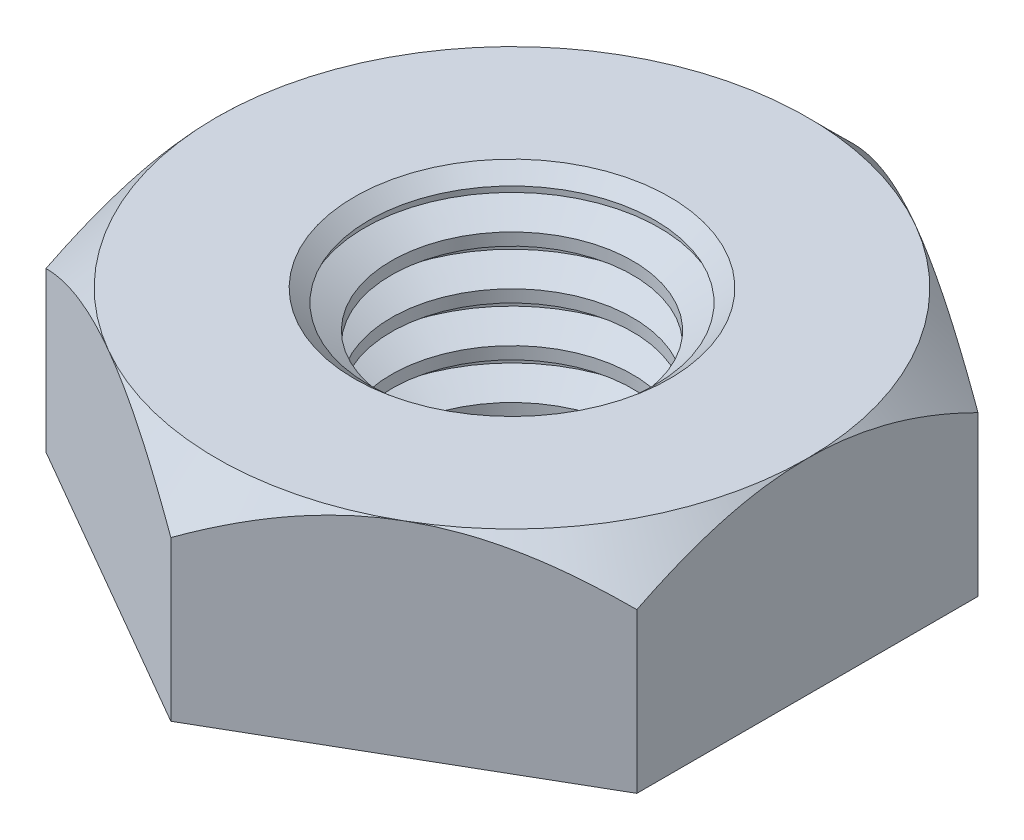
SolidWorks part; units mm, degrees
ref_plane "Front" through (0, 0, 0) normal (0, 0, 1) x (1, 0, 0)
ref_plane "Top" through (0, 0, 0) normal (0, 1, 0) x (1, 0, 0)
ref_plane "Right" through (0, 0, 0) normal (1, 0, 0) x (0, 0, -1)
sketch "Sketch1" plane through (0, 0, 0) normal (0, 1, 0) x (1, 0, 0)
  line L1 (0, 5.4993) -> (-4.7625, 2.7496)
  line L2 (-4.7625, 2.7496) -> (-4.7625, -2.7496)
  line L3 (-4.7625, -2.7496) -> (0, -5.4993)
  line L4 (0, -5.4993) -> (4.7625, -2.7496)
  line L5 (4.7625, -2.7496) -> (4.7625, 2.7496)
  line L6 (4.7625, 2.7496) -> (0, 5.4993)
  circle A0 centre (0, 0) radius 4.7625 construction
extrude "Extrude1" add sketch "Sketch1" along normal blind 3.302
sketch "Sketch3" plane through (0, 0, 0) normal (1, 0, 0) x (0, 0, -1)
  line L0 (4.7625, 3.302) -> (5.4993, 2.5652)
  line L1 (2.7496, 3.302) -> (5.4993, 3.302) construction
  line L2 (5.4993, 3.302) -> (5.4993, 0) construction
  line L3 (5.4993, 2.5652) -> (5.4993, 3.302)
  line L4 (5.4993, 3.302) -> (4.7625, 3.302)
  line L5 (0, 0.542) -> (0, -0.542) construction
  dimension "D1" = 45
revolve "Cut-Revolve2" cut sketch "Sketch3" angle 360 about L5
sketch "Sketch2" plane through (0, 0, 0) normal (0, 0, 1) x (1, 0, 0)
  line L0 (0, 1.6636) -> (0, -0.3796) construction
  line L1 (0, 3.302) -> (1.9453, 3.302)
  line L3 (0, 3.302) -> (4.7625, 3.302) construction
  line L4 (0, 2.5082) -> (1.9453, 2.5082)
  line L5 (1.9453, 3.302) -> (2.3749, 3.054)
  line L6 (2.3749, 3.054) -> (2.3749, 2.9547)
  line L7 (2.3749, 2.9547) -> (1.9453, 2.7067)
  line L9 (1.9453, 2.5082) -> (1.9453, 2.7067)
  line L10 (0, 2.5082) -> (0, 3.302)
  line L11 (1.9453, 3.302) -> (1.9453, 2.7067) construction
  line L12 (2.3749, 3.0043) -> (1.9453, 3.0043) construction
  dimension "D1" = 60
revolve "Cut-Revolve1" cut sketch "Sketch2" angle 360 about L0
pattern_linear "LPattern2" count 5 spacing 0.7937 along (0, -1, 0) of "Cut-Revolve1"
chamfer "Chamfer1" distance 0.5953 angle 41 1 edges at (0, 3.302, 1.9453) first distance on face at (0, 3.302, 0)
equation "\"D5@Sketch2\"=\"Pitch@Sketch2\"/8"
equation "\"D2@Sketch2\"=\"Pitch@Sketch2\"/4"
equation "\"D3@LPattern2\"=\"Pitch@Sketch2\""
equation "\"D1@LPattern2\"=\"Height@Extrude1\"/\"Pitch@Sketch2\"+.5"
equation "\"D2@Sketch3\"=\"Hex Flats@Sketch1\""
equation "\"D1@Chamfer1\"=\"Pitch@Sketch2\"*.75"
